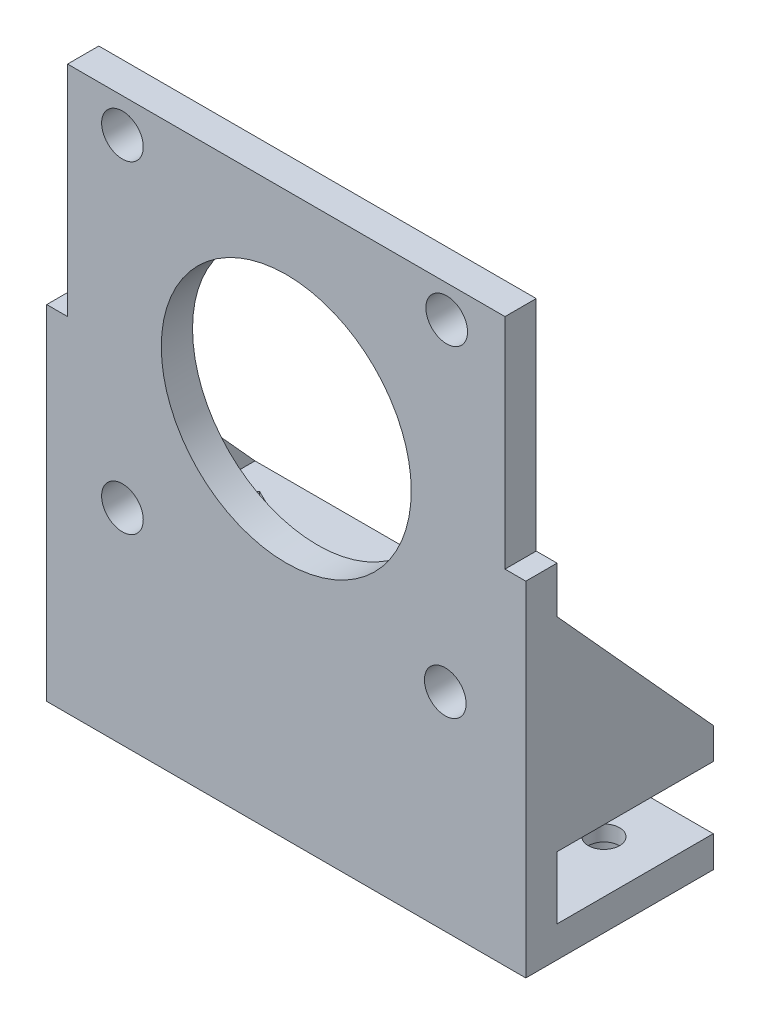
SolidWorks part; units mm, degrees
note: The reader was unsure of these and kept them because the rebuilt part matched: shared geometry of "Esboço1<3>", "Esboço2<4>".
ref_plane "Plano frontal" through (0, 0, 0) normal (0, 0, 1) x (1, 0, 0)
ref_plane "Plano superior" through (0, 0, 0) normal (0, 1, 0) x (1, 0, 0)
ref_plane "Plano direito" through (0, 0, 0) normal (1, 0, 0) x (0, 0, -1)
sketch "Esboço1" plane through (0, 0, 0) normal (0, 0, 1) x (1, 0, 0)
  line L2 (-23, -23) -> (-23, -2)
  line L4 (-21, 19) -> (21, 19)
  line L5 (-23, -2) -> (-21, -2)
  line L6 (-21, -2) -> (-21, 19)
  line L7 (-23, -23) -> (23, -23)
  line L8 (-23, -23) -> (-23, -2)
  line L10 (23, -23) -> (23, 0)
  line L11 (21, 19) -> (21, -2)
  line L12 (21, -2) -> (23, -2)
  line L13 (-23, -23) -> (23, -23)
  line L14 (-23, -23) -> (-23, -32)
  line L15 (-23, -32) -> (23, -32)
  line L16 (23, -23) -> (23, -32)
  line L17 (-23, -23) -> (23, -23)
  line L18 (-23, -23) -> (-23, -26)
  line L19 (-23, -26) -> (23, -26)
  line L20 (23, -23) -> (23, -26)
  line L21 (-23, -26) -> (23, -26)
  line L22 (-23, -26) -> (-23, -25)
  line L23 (-23, -32) -> (23, -32)
  line L24 (23, -26) -> (23, -25)
  line L25 (-23, -32) -> (-23, -35)
  line L26 (-23, -35) -> (23, -35)
  line L27 (23, -32) -> (23, -35)
  line L30 (-14.3443, 14.291) -> (13.7809, -13.7297) construction
  line L31 (-14.1049, -14.1049) -> (14.2792, 14.2792) construction
  circle A0 centre (-15.7317, -15.2683) radius 2
  circle A1 centre (-15.7317, 15.7317) radius 2
  circle A2 centre (15.405, 15.9323) radius 2
  circle A3 centre (15.2677, -15.0674) radius 2
  circle A4 centre (0, 0) radius 12
  point P0 (0, 0)
  point P3 (0, 0)
  point P6 (-14.7929, 14.7929)
  dimension "D8" = 4
  dimension "D9" = 4
  dimension "D10" = 4
  dimension "D11" = 4
  dimension "D12" = 24
  dimension "D1" = 31
  dimension "D2" = 42
  dimension "D3" = 31
  dimension "D4" = 31
  dimension "D5" = 9
  dimension "D6" = 3
  dimension "D7" = 3
extrude "Ressalto-extrusão1" add sketch "Esboço1" along normal blind 3
extrude "Ressalto-extrusão2" add sketch "Esboço1<3>" against normal blind 15 contours L14 L19 L16 L7 | L27 L15 L25 L26
sketch "Esboço1<3>" plane through (0, 0, 0) normal (0, 0, 1) x (1, 0, 0) same geometry as "Esboço1"
sketch "Esboço2" plane through (0, -35, 0) normal (0, -1, 0) x (1, 0, 0)
  line L0 (-18, 3) -> (-18, 0)
  line L1 (-23, 3) -> (23, 3) construction
  line L2 (-18, 0) -> (-18, -9.5)
  line L3 (-23, -9.5) -> (-18, -9.5)
  line L4 (-23, 3) -> (-23, -15) construction
  line L5 (-18, -7.25) -> (-18, 0)
  line L6 (0, 3) -> (0, -15) construction
  line L7 (-23, -15) -> (23, -15) construction
  line L8 (23, -9.5) -> (18, -9.5)
  circle A0 centre (-18, -9.5) radius 2.25
  circle A1 centre (18, -9.5) radius 2.25
  circle A2 centre (-18, -9.5) radius 1.5
  circle A3 centre (18, -9.5) radius 1.5
  dimension "D4" = 4.5
  dimension "D5" = 3
  dimension "D6" = 3
  dimension "D1" = 3
  dimension "D2" = 9.5
  dimension "D3" = 5
extrude "Corte-extrusão1" cut sketch "Esboço2" against normal blind 1.5
extrude "Corte-extrusão3" cut sketch "Esboço2<4>" against normal through all
sketch "Esboço2<4>" plane through (0, -35, 0) normal (0, -1, 0) x (1, 0, 0) same geometry as "Esboço2"
sketch "Esboço5" plane through (23, 0, 0) normal (1, 0, 0) x (0, 0, -1)
  line L0 (15, -23) -> (0, -6.4554)
  line L1 (0, -23) -> (0, -2) construction
  line L2 (0, -6.4554) -> (0, -23)
  line L3 (15, -23) -> (0, -23) construction
  line L4 (0, -23) -> (15, -23)
extrude "Ressalto-extrusão3" add sketch "Esboço5" against normal blind 2
sketch "Esboço6" plane through (-23, 0, 0) normal (-1, 0, 0) x (0, 0, 1)
  line L0 (-15, -23) -> (0, -23)
  line L1 (0, -23) -> (-15, -23) construction
  line L2 (-15, -23) -> (0, -23) construction
  line L3 (0, -23) -> (0, -6.4554)
  line L4 (0, -6.4554) -> (-15, -23)
extrude "Ressalto-extrusão4" add sketch "Esboço6" against normal blind 2
sketch "Esboço7" plane through (0, -23, 0) normal (0, 1, 0) x (1, 0, 0)
  line L0 (0, 0) -> (0, 9.3086)
  line L1 (-15.1462, 8.1075) -> (-15.3672, 11.2753)
  line L2 (-15.3672, 11.2753) -> (-18.221, 12.6677)
  line L3 (-18.221, 12.6677) -> (-20.8538, 10.8925)
  line L4 (-20.8538, 10.8925) -> (-20.6328, 7.7247)
  line L5 (-20.6328, 7.7247) -> (-17.779, 6.3323)
  line L6 (-17.779, 6.3323) -> (-15.1462, 8.1075)
  line L7 (-21, 0) -> (21, 0) construction
  line L8 (20.6328, 7.7247) -> (17.779, 6.3323)
  line L9 (20.8538, 10.8925) -> (20.6328, 7.7247)
  line L10 (18.221, 12.6677) -> (20.8538, 10.8925)
  line L11 (15.3672, 11.2753) -> (18.221, 12.6677)
  line L12 (15.1462, 8.1075) -> (15.3672, 11.2753)
  line L13 (17.779, 6.3323) -> (15.1462, 8.1075)
  circle A0 centre (-18, 9.5) radius 2.75 construction
  circle M7 centre (-18, 9.5) radius 1.5
  circle M8 centre (18, 9.5) radius 1.5
extrude "Corte-extrusão4" cut sketch "Esboço7" against normal blind 2 contours L5 L6 L1 L2 L3 L4 M7 | L13 L8 L9 L10 L11 L12 M8
